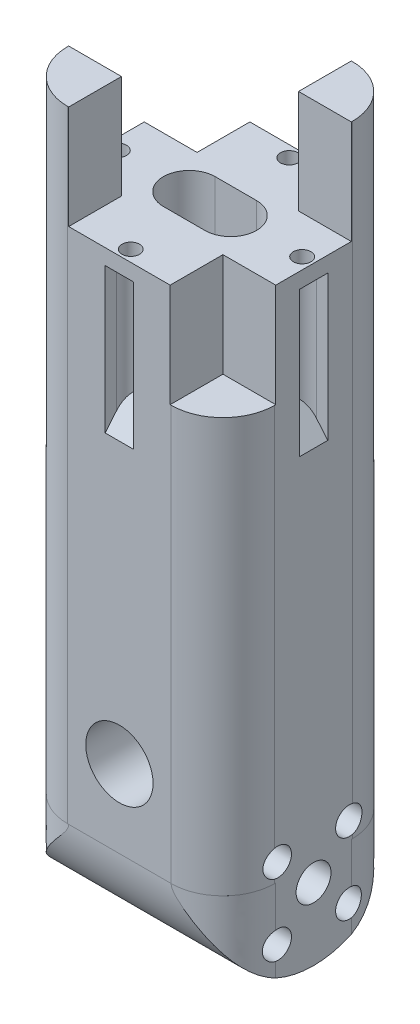
SolidWorks part; units mm, degrees
ref_plane "Plan de face" through (0, 0, 0) normal (0, 0, 1) x (1, 0, 0)
ref_plane "Plan de dessus" through (0, 0, 0) normal (0, 1, 0) x (1, 0, 0)
ref_plane "Plan de droite" through (0, 0, 0) normal (1, 0, 0) x (0, 0, -1)
sketch "Esquisse3" plane through (0, 0, 0) normal (0, 1, 0) x (1, 0, 0)
  line L1 (-20, -17.5) -> (20, -17.5)
  line L2 (-20, -17.5) -> (-20, 17.5)
  line L3 (-20, 17.5) -> (20, 17.5)
  line L4 (20, -17.5) -> (20, 17.5)
  line L5 (-20, -17.5) -> (20, 17.5) construction
  line L6 (-20, 17.5) -> (20, -17.5) construction
  point P0 (0, 0)
  dimension "D1" = 40
  dimension "D2" = 35
extrude "Boss.-Extru.2" add sketch "Esquisse3" along normal blind 120
fillet "Congé1" radius 10 4 edges at (-20, 60, -17.5) (-20, 60, 17.5) (20, 60, -17.5) (20, 60, 17.5)
sketch "Esquisse4" plane through (0, 120, 0) normal (0, 1, 0) x (1, 0, 0)
  line L10 (-20, 17.5) -> (9.8, 17.5)
  line L11 (9.8, 17.5) -> (9.8, 7.3)
  line L12 (9.8, 7.3) -> (20, 7.3)
  line L13 (20, 7.3) -> (20, -17.5)
  line L14 (20, -17.5) -> (-9.8, -17.5)
  line L15 (-9.8, -17.5) -> (-9.8, -7.3)
  line L16 (-9.8, -7.3) -> (-20, -7.3)
  line L17 (-20, -7.3) -> (-20, 17.5)
  line L19 (20, -7.5) -> (20, 7.5) construction
  line L20 (10, 17.5) -> (-10, 17.5) construction
  line L21 (-20, 7.5) -> (-20, -7.5) construction
  line L22 (-10, -17.5) -> (10, -17.5) construction
  arc A0 (-20, -7.5) -> (-10, -17.5) centre (-10, -7.5) ccw construction
  arc A1 (20, 7.5) -> (10, 17.5) centre (10, 7.5) ccw construction
  dimension "D4" = 0.2
  dimension "D1" = 0.2
  dimension "D2" = 0.2
  dimension "D3" = 0.2
extrude "Enlèv. mat.-Extru.1" cut sketch "Esquisse4" against normal blind 20
sketch "Esquisse5" plane through (0, 100, 0) normal (0, 1, 0) x (1, 0, 0)
  line L0 (-20, 7.5) -> (-20, -7.3) construction
  line L9 (-20, 17.5) -> (-9.8, 17.5)
  line L10 (-20, 17.5) -> (-20, 7.3)
  line L11 (-20, 7.3) -> (-9.8, 7.3)
  line L12 (-9.8, 17.5) -> (-9.8, 7.3)
  line L13 (20, -17.5) -> (9.8, -17.5)
  line L14 (20, -17.5) -> (20, -7.3)
  line L15 (20, -7.3) -> (9.8, -7.3)
  line L16 (9.8, -17.5) -> (9.8, -7.3)
  line L17 (9.8, 17.5) -> (-10, 17.5) construction
  line L18 (20, -7.5) -> (20, 7.3) construction
  line L19 (-9.8, -17.5) -> (10, -17.5) construction
  arc A0 (-10, 17.5) -> (-20, 7.5) centre (-10, 7.5) ccw construction
  arc A1 (10, -17.5) -> (20, -7.5) centre (10, -7.5) ccw construction
  dimension "D2" = 0.2
  dimension "D1" = 0.2
  dimension "D3" = 0.2
  dimension "D4" = 0.2
extrude "Enlèv. mat.-Extru.2" cut sketch "Esquisse5" against normal blind 20
sketch "Esquisse6" plane through (0, 100, 0) normal (0, 1, 0) x (1, 0, 0)
  line L0 (-4, 0) -> (4, 0) construction
  line L1 (-4, 5) -> (4, 5)
  line L2 (-4, -5) -> (4, -5)
  arc A0 (-4, 5) -> (-4, -5) centre (-4, 0) ccw
  arc A1 (4, -5) -> (4, 5) centre (4, 0) ccw
  point P2 (0, 0)
  dimension "D2" = 5
  dimension "D1" = 8
extrude "Enlèv. mat.-Extru.3" cut sketch "Esquisse6" against normal blind 90
sketch "Esquisse8" plane through (-20, 0, 0) normal (-1, 0, 0) x (0, 0, 1)
  line L0 (-7.5, 0) -> (7.5, 0) construction
  line L1 (17.5, 120) -> (17.5, 0) construction
  line L2 (-17.5, 0) -> (17.5, 0)
  arc A0 (-17.5, 0) -> (17.5, 0) centre (0, 0) ccw
extrude "Boss.-Extru.3" add sketch "Esquisse8" against normal blind 40
sketch "Esquisse10" plane through (0, 0, 0) normal (0, 1, 0) x (1, 0, 0)
  line L1 (-9.75, -10.55) -> (-2.55, -10.55)
  line L2 (-9.75, -10.55) -> (-9.75, 10.55)
  line L3 (-9.75, 10.55) -> (-2.55, 10.55)
  line L4 (-2.55, -10.55) -> (-2.55, 10.55)
  line L5 (2.55, -10.55) -> (9.75, -10.55)
  line L6 (2.55, -10.55) -> (2.55, 10.55)
  line L7 (2.55, 10.55) -> (9.75, 10.55)
  line L8 (9.75, -10.55) -> (9.75, 10.55)
  dimension "D1" = 7.2
  dimension "D2" = 7.2
  dimension "D3" = 21.1
  dimension "D4" = 21.1
  dimension "D5" = 2.55
  dimension "D6" = 2.55
  dimension "D7" = 10.55
extrude "Enlèv. mat.-Extru.5" cut sketch "Esquisse10" against normal through all and the other way blind 6.8
sketch "Esquisse12" plane through (2.55, 0, 0) normal (1, 0, 0) x (0, 0, -1)
  line L0 (-10.55, -13.9624) -> (10.55, -13.9624) construction
  line L1 (6.5, -40.1276) -> (-6.5, -40.1276)
  line L2 (6.5, -40.1276) -> (6.5, 5.1276)
  line L3 (6.5, 5.1276) -> (-6.5, 5.1276)
  line L4 (-6.5, -40.1276) -> (-6.5, 5.1276)
  line L5 (6.5, -40.1276) -> (-6.5, 5.1276) construction
  line L6 (6.5, 5.1276) -> (-6.5, -40.1276) construction
  arc A0 (-10.55, -13.9624) -> (10.55, -13.9624) centre (0, 0) ccw construction
  point P0 (0, -17.5)
  dimension "D1" = 13
  dimension "D2" = 19.09
extrude "Enlèv. mat.-Extru.7" cut sketch "Esquisse12" against normal blind 6
hole_wizard "Trous de centrage Ø1.0mm1" positions "Esquisse13" profile "Esquisse14" hole size "Ø1.0" standard "Ansi Metric" end condition through all
sketch "Esquisse13" plane through (20, 0, 0) normal (1, 0, 0) x (0, 0, -1)
  arc A1 (-17.5, 0) -> (17.5, 0) centre (0, 0) ccw construction
  point P0 (0, -3.6)
  point P10 (0, -17.5)
  dimension "D1" = 13.9
sketch "Esquisse14" plane through (20, -3.6, 0) normal (0, 1, 0) x (0, 0, -1)
  line L0 (0, 0) -> (0, 40)
  line L1 (0, 40) -> (3.3734, 40)
  line L2 (3.3734, 40) -> (3.3734, 0)
  line L5 (3.3734, 0) -> (0, 0)
  line L11 (0, -6.35) -> (0, 107.95) construction
  dimension "Diamètre du perçage jusqu'au prochain" = 6.7469
  dimension "Profondeur du perçage jusqu'au prochain" = 40
hole_wizard "Dégagement M51" positions "Esquisse15" profile "Esquisse16" hole size "M5" standard "Ansi Metric"
sketch "Esquisse15" plane through (-20, 0, 0) normal (-1, 0, 0) x (0, 0, 1)
  circle A0 centre (0, -3.6) radius 3.3734 construction
  point P0 (-6.915, -10.515)
  point P2 (-6.915, 3.315)
  point P4 (6.915, 3.315)
  point P6 (6.915, -10.515)
  dimension "D6" = 6.915
  dimension "D1" = 13.83
  dimension "D2" = 13.83
  dimension "D3" = 13.83
  dimension "D4" = 13.83
  dimension "D5" = 6.915
sketch "Esquisse16" plane through (-20, -10.515, -6.915) normal (0, 1, 0) x (0, 0, 1)
  line L0 (0, 0) -> (0, 13.6524)
  line L1 (0, 13.6524) -> (2.75, 12)
  line L2 (2.75, 12) -> (2.75, 0)
  line L5 (2.75, 0) -> (0, 0)
  line L10 (0, 13.6524) -> (-2.75, 12) construction
  line L11 (0, -6.35) -> (0, 107.95) construction
  dimension "Diamètre du perçage" = 5.5
  dimension "Profondeur du perçage" = 12
  dimension "Angle de pointe" = 118
hole_wizard "Dégagement M52" positions "Esquisse19" profile "Esquisse20" hole size "M5" standard "Ansi Metric" end condition through all
sketch "Esquisse19" plane through (20, 0, 0) normal (1, 0, 0) x (0, 0, -1)
  circle A0 centre (0, -3.6) radius 3.3734 construction
  point P0 (-6.915, -10.515)
  point P2 (6.915, -10.515)
  point P4 (6.915, 3.315)
  point P6 (-6.915, 3.315)
  dimension "D4" = 6.915
  dimension "D1" = 13.83
  dimension "D2" = 13.83
  dimension "D3" = 6.915
sketch "Esquisse20" plane through (20, -10.515, 6.915) normal (0, 1, 0) x (0, 0, -1)
  line L0 (0, 0) -> (0, 40)
  line L1 (0, 40) -> (2.65, 40)
  line L2 (2.65, 40) -> (2.65, 0)
  line L5 (2.65, 0) -> (0, 0)
  line L11 (0, -6.35) -> (0, 107.95) construction
  dimension "Diamètre du perçage jusqu'au prochain" = 5.3
  dimension "Profondeur du perçage jusqu'au prochain" = 40
sketch "Esquisse21" plane through (0, 100, 0) normal (0, 1, 0) x (1, 0, 0)
  line L0 (-9.8, -17.5) -> (9.8, -17.5) construction
  line L1 (-20, 7.3) -> (-20, -7.3) construction
  circle A0 centre (0, -15.3) radius 1.7
  circle A1 centre (-17.8, 0) radius 1.7
  dimension "D1" = 3.4
  dimension "D2" = 2.2
  dimension "D3" = 2.2
extrude "Enlèv. mat.-Extru.8" cut sketch "Esquisse21" against normal blind 3
sketch "Esquisse22" plane through (0, 97, 0) normal (0, 1, 0) x (1, 0, 0)
  circle A0 centre (-17.8, 0) radius 2.75
  dimension "D1" = 5.5
extrude "Enlèv. mat.-Extru.9" cut sketch "Esquisse22" against normal blind 20
sketch "Esquisse23" plane through (0, 97, 0) normal (0, 1, 0) x (1, 0, 0)
  circle A0 centre (0, -15.3) radius 2.75
  dimension "D1" = 5.5
extrude "Enlèv. mat.-Extru.10" cut sketch "Esquisse23" against normal blind 20
sketch "Esquisse24" plane through (-20, 0, 0) normal (-1, 0, 0) x (0, 0, 1)
  line L0 (-1.65, 97) -> (1.65, 97) construction
  line L1 (2.75, 97) -> (-2.75, 97)
  line L2 (2.75, 97) -> (2.75, 77)
  line L3 (2.75, 77) -> (-2.75, 77)
  line L4 (-2.75, 97) -> (-2.75, 77)
  line L5 (2.75, 97) -> (-2.75, 77) construction
  line L6 (2.75, 77) -> (-2.75, 97) construction
  line L7 (-1.65, 77) -> (1.65, 77) construction
  point P0 (0, 87)
  dimension "D1" = 5.5
extrude "Enlèv. mat.-Extru.11" cut sketch "Esquisse24" against normal blind 2.2
sketch "Esquisse25" plane through (0, 0, 17.5) normal (0, 0, 1) x (1, 0, 0)
  line L1 (2.75, 97) -> (-2.75, 97)
  line L2 (2.75, 97) -> (2.75, 77)
  line L3 (2.75, 77) -> (-2.75, 77)
  line L4 (-2.75, 97) -> (-2.75, 77)
  line L5 (2.75, 97) -> (-2.75, 77) construction
  line L6 (2.75, 77) -> (-2.75, 97) construction
  line L7 (-1.65, 97) -> (1.65, 97) construction
  line L8 (-1.65, 77) -> (1.65, 77) construction
  point P0 (0, 87)
  dimension "D1" = 5.5
extrude "Enlèv. mat.-Extru.12" cut sketch "Esquisse25" against normal blind 2.2
mirror "Symétrie2" about plane through (0, 0, 0) normal (1, 0, 0) of "Enlèv. mat.-Extru.11", "Enlèv. mat.-Extru.9", "Enlèv. mat.-Extru.8"
mirror "Symétrie3" about plane through (0, 0, 0) normal (0, 0, 1) of "Enlèv. mat.-Extru.12", "Enlèv. mat.-Extru.10", "Enlèv. mat.-Extru.8"
chamfer "Chanfrein1" distance 8 angle 40 4 edges at (-20, 77, 0) (0, 77, 17.5) (20, 77, 0) (0, 77, -17.5) first distance on face at (-20, 42.5543, 0) first distance on face at (0, 75, 17.5) first distance on face at (20, 42.5543, 0) first distance on face at (0, 75, -17.5)
sketch "Esquisse26" plane through (0, 0, 0) normal (0, 1, 0) x (1, 0, 0)
  line L0 (-9.8, 17.5) -> (-20, 17.5)
  line L2 (9.8, 17.5) -> (20, 17.5)
  line L3 (20, 17.5) -> (20, 7.3)
  line L5 (-9.8, -17.5) -> (-20, -17.5)
  line L6 (-20, -17.5) -> (-20, -7.3)
  line L7 (20, -7.3) -> (20, -17.5)
  line L9 (-20, 17.5) -> (-20, 7.5)
  line L10 (20, -17.5) -> (10, -17.5)
  arc A1 (20, 7.5) -> (10, 17.5) centre (10, 7.5) ccw construction
  arc A2 (-20, -7.5) -> (-10, -17.5) centre (-10, -7.5) ccw construction
  arc A4 (-10, 17.5) -> (-20, 7.5) centre (-10, 7.5) ccw construction
  arc A5 (10, -17.5) -> (20, -7.5) centre (10, -7.5) ccw construction
  spline S0 degree 2 poles (-20, 7.5) (-19.1208, 16.7623) (-9.8, 17.5) knots 0 0 0 1 1 1
  spline S1 degree 2 poles (9.8, 17.5) (19.2421, 16.7421) (20, 7.3) knots 0 0 0 1 1 1
  spline S2 degree 2 poles (-20, -7.3) (-19.2421, -16.7421) (-9.8, -17.5) knots 0 0 0 1 1 1
  spline S3 degree 2 poles (10, -17.5) (19.2623, -16.6208) (20, -7.3) knots 0 0 0 1 1 1
extrude "Enlèv. mat.-Extru.13" cut sketch "Esquisse26" against normal through all
sketch "Esquisse27" plane through (0, 0, 17.5) normal (0, 0, 1) x (1, 0, 0)
  line L0 (-9.8, 100) -> (9.8, 100) construction
  line L1 (20, 80) -> (20, 5.8996) construction
  circle A0 centre (0, 15) radius 6.5
  dimension "D2" = 13
  dimension "D1" = 85
  dimension "D3" = 20
extrude "Enlèv. mat.-Extru.14" cut sketch "Esquisse27" against normal through all
